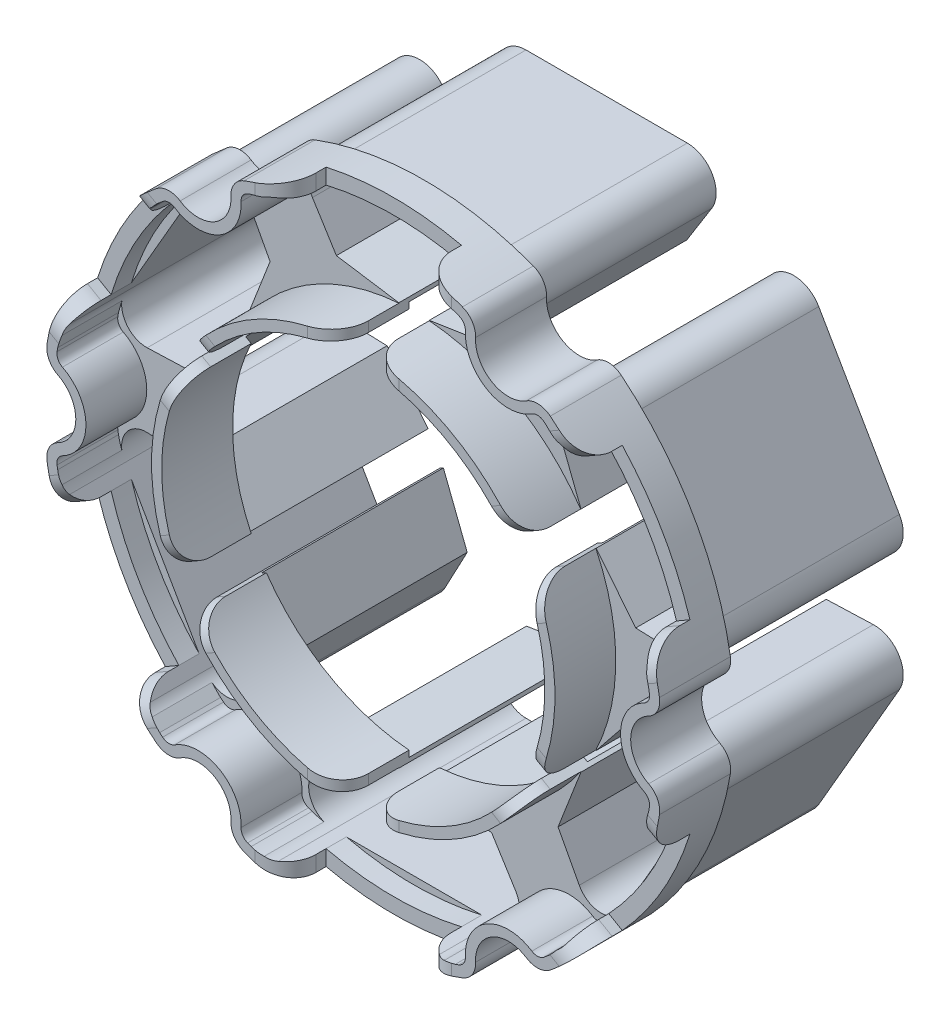
SolidWorks part; units mm, degrees
ref_plane "Ön Düzlem" through (0, 0, 0) normal (0, 0, 1) x (1, 0, 0)
ref_plane "Üst Düzlem" through (0, 0, 0) normal (0, 1, 0) x (1, 0, 0)
ref_plane "Sağ Düzlem" through (0, 0, 0) normal (1, 0, 0) x (0, 0, -1)
sketch "Çizim2" plane through (0, 0, 0) normal (0, 0, 1) x (1, 0, 0)
  line L0 (-1.5, 18.3137) -> (-1.5, 19.3137) construction
  line L13 (1.5, 18.3137) -> (1.5, 19.3137) construction
  line L14 (1.5, 19.3137) -> (8, 20.3137) construction
  line L15 (-1.5, 19.3137) -> (-8, 20.3137) construction
  line L16 (8, 20.3137) -> (10.5, 24.3137) construction
  line L17 (-8, 20.3137) -> (-10.5, 24.3137) construction
  line L18 (-7.956, 28.9037) -> (7.956, 28.9037) construction
  line L20 (-1.5, 19.4654) -> (-7.9092, 20.4515)
  line L21 (-7.9092, 20.4515) -> (-10.3728, 24.3932)
  line L22 (-7.956, 28.7537) -> (7.956, 28.7537)
  line L23 (7.9092, 20.4515) -> (10.3728, 24.3932)
  line L24 (1.5, 19.4654) -> (7.9092, 20.4515)
  line L27 (1.5, 19.8803) -> (7.6612, 20.8281)
  line L28 (7.6612, 20.8281) -> (10.0251, 24.6105)
  line L29 (-7.956, 28.3437) -> (7.956, 28.3437)
  line L30 (-7.6612, 20.8281) -> (-10.0251, 24.6105)
  line L31 (-1.5, 19.8803) -> (-7.6612, 20.8281)
  line L120 (-0.94, 18.3137) -> (-0.94, 19.7941) construction
  line L121 (-1.35, 18.3137) -> (-1.35, 19.4424) construction
  line L122 (1.35, 18.3137) -> (1.35, 19.4424) construction
  line L123 (0.94, 18.3137) -> (0.94, 19.7941) construction
  line L133 (-0.94, 19.7941) -> (-7.6612, 20.8281) construction
  line L134 (0.94, 19.7941) -> (7.6612, 20.8281) construction
  line L145 (-1.5, 19.8803) -> (-1.5, 19.4654)
  line L146 (1.5, 19.8803) -> (1.5, 19.4654)
  line L147 (17.8718, 8.7595) -> (21.8683, 3.7793) [skipped]
  line L148 (21.8683, 3.7793) -> (26.3259, 3.6232) [skipped]
  line L149 (20.5683, 21.0619) -> (28.5243, 7.2817) [skipped]
  line L150 (14.2071, 17.0488) -> (16.3007, 20.9872) [skipped]
  line L151 (16.5218, 11.0977) -> (14.2071, 17.0488) [skipped]
  line L152 (-1.35, 19.4424) -> (-7.9092, 20.4515) construction
  line L153 (16.1626, 10.8903) -> (13.7569, 17.0753) [skipped]
  line L154 (13.7569, 17.0753) -> (15.9387, 21.1797) [skipped]
  line L155 (20.9234, 21.2669) -> (28.8794, 7.4867) [skipped]
  line L156 (21.6661, 3.3761) -> (26.3115, 3.2135) [skipped]
  line L157 (17.5126, 8.552) -> (21.6661, 3.3761) [skipped]
  line L158 (1.35, 19.4424) -> (7.9092, 20.4515) construction
  line L159 (-17.8718, 8.7595) -> (-21.8683, 3.7793) [skipped]
  line L160 (-21.8683, 3.7793) -> (-26.3259, 3.6232) [skipped]
  line L161 (-28.5243, 7.2817) -> (-20.5683, 21.0619) [skipped]
  line L162 (-14.2071, 17.0488) -> (-16.3007, 20.9872) [skipped]
  line L163 (-16.5218, 11.0977) -> (-14.2071, 17.0488) [skipped]
  line L164 (16.4668, 11.2392) -> (14.2071, 17.0488)
  line L165 (-16.1626, 10.8903) -> (-13.7569, 17.0753) [skipped]
  line L166 (-13.7569, 17.0753) -> (-15.9387, 21.1797) [skipped]
  line L167 (-28.8794, 7.4867) -> (-20.9234, 21.2669) [skipped]
  line L168 (-21.6661, 3.3761) -> (-26.3115, 3.2135) [skipped]
  line L169 (-17.5126, 8.552) -> (-21.6661, 3.3761) [skipped]
  line L170 (14.2071, 17.0488) -> (16.3007, 20.9872)
  line L171 (17.5126, -8.552) -> (21.6661, -3.3761) [skipped]
  line L172 (21.6661, -3.3761) -> (26.3115, -3.2135) [skipped]
  line L173 (28.8794, -7.4867) -> (20.9234, -21.2669) [skipped]
  line L174 (13.7569, -17.0753) -> (15.9387, -21.1797) [skipped]
  line L175 (16.1626, -10.8903) -> (13.7569, -17.0753) [skipped]
  line L176 (20.5683, 21.0619) -> (28.5243, 7.2817)
  line L177 (16.5218, -11.0977) -> (14.2071, -17.0488) [skipped]
  line L178 (14.2071, -17.0488) -> (16.3007, -20.9872) [skipped]
  line L179 (28.5243, -7.2817) -> (20.5683, -21.0619) [skipped]
  line L180 (21.8683, -3.7793) -> (26.3259, -3.6232) [skipped]
  line L181 (17.8718, -8.7595) -> (21.8683, -3.7793) [skipped]
  line L182 (21.8683, 3.7793) -> (26.3259, 3.6232)
  line L183 (1.35, -19.4424) -> (7.9092, -20.4515) [skipped]
  line L184 (7.9092, -20.4515) -> (10.3728, -24.3932) [skipped]
  line L185 (7.956, -28.7537) -> (-7.956, -28.7537) [skipped]
  line L186 (-7.9092, -20.4515) -> (-10.3728, -24.3932) [skipped]
  line L187 (-1.35, -19.4424) -> (-7.9092, -20.4515) [skipped]
  line L188 (17.9668, 8.6411) -> (21.8683, 3.7793)
  line L189 (-1.35, -19.8572) -> (-7.6612, -20.8281) [skipped]
  line L190 (-7.6612, -20.8281) -> (-10.0251, -24.6105) [skipped]
  line L191 (7.956, -28.3437) -> (-7.956, -28.3437) [skipped]
  line L192 (7.6612, -20.8281) -> (10.0251, -24.6105) [skipped]
  line L193 (1.35, -19.8572) -> (7.6612, -20.8281) [skipped]
  line L194 (17.9668, 8.6411) -> (17.6076, 8.4337)
  line L195 (-16.1626, -10.8903) -> (-13.7569, -17.0753) [skipped]
  line L196 (-13.7569, -17.0753) -> (-15.9387, -21.1797) [skipped]
  line L197 (-20.9234, -21.2669) -> (-28.8794, -7.4867) [skipped]
  line L198 (-21.6661, -3.3761) -> (-26.3115, -3.2135) [skipped]
  line L199 (-17.5126, -8.552) -> (-21.6661, -3.3761) [skipped]
  line L200 (17.6076, 8.4337) -> (21.6661, 3.3761)
  line L201 (-17.8718, -8.7595) -> (-21.8683, -3.7793) [skipped]
  line L202 (-21.8683, -3.7793) -> (-26.3259, -3.6232) [skipped]
  line L203 (-20.5683, -21.0619) -> (-28.5243, -7.2817) [skipped]
  line L204 (-14.2071, -17.0488) -> (-16.3007, -20.9872) [skipped]
  line L205 (-16.5218, -11.0977) -> (-14.2071, -17.0488) [skipped]
  line L206 (21.6661, 3.3761) -> (26.3115, 3.2135)
  line L207 (20.9234, 21.2669) -> (28.8794, 7.4867)
  line L208 (13.7569, 17.0753) -> (15.9387, 21.1797)
  line L209 (16.1076, 11.0318) -> (13.7569, 17.0753)
  line L210 (16.4668, 11.2392) -> (16.1076, 11.0318)
  line L211 (17.9668, -8.6411) -> (21.8683, -3.7793)
  line L212 (21.8683, -3.7793) -> (26.3259, -3.6232)
  line L213 (28.5243, -7.2817) -> (20.5683, -21.0619)
  line L214 (14.2071, -17.0488) -> (16.3007, -20.9872)
  line L215 (16.4668, -11.2392) -> (14.2071, -17.0488)
  line L216 (16.4668, -11.2392) -> (16.1076, -11.0318)
  line L217 (16.1076, -11.0318) -> (13.7569, -17.0753)
  line L218 (13.7569, -17.0753) -> (15.9387, -21.1797)
  line L219 (28.8794, -7.4867) -> (20.9234, -21.2669)
  line L220 (21.6661, -3.3761) -> (26.3115, -3.2135)
  line L221 (17.6076, -8.4337) -> (21.6661, -3.3761)
  line L222 (17.9668, -8.6411) -> (17.6076, -8.4337)
  line L223 (1.5, -19.8803) -> (7.6612, -20.8281)
  line L224 (7.6612, -20.8281) -> (10.0251, -24.6105)
  line L225 (7.956, -28.3437) -> (-7.956, -28.3437)
  line L226 (-7.6612, -20.8281) -> (-10.0251, -24.6105)
  line L227 (-1.5, -19.8803) -> (-7.6612, -20.8281)
  line L228 (-1.5, -19.8803) -> (-1.5, -19.4654)
  line L229 (-1.5, -19.4654) -> (-7.9092, -20.4515)
  line L230 (-7.9092, -20.4515) -> (-10.3728, -24.3932)
  line L231 (7.956, -28.7537) -> (-7.956, -28.7537)
  line L232 (7.9092, -20.4515) -> (10.3728, -24.3932)
  line L233 (1.5, -19.4654) -> (7.9092, -20.4515)
  line L234 (1.5, -19.8803) -> (1.5, -19.4654)
  line L235 (-16.4668, -11.2392) -> (-14.2071, -17.0488)
  line L236 (-14.2071, -17.0488) -> (-16.3007, -20.9872)
  line L237 (-20.5683, -21.0619) -> (-28.5243, -7.2817)
  line L238 (-21.8683, -3.7793) -> (-26.3259, -3.6232)
  line L239 (-17.9668, -8.6411) -> (-21.8683, -3.7793)
  line L240 (-17.9668, -8.6411) -> (-17.6076, -8.4337)
  line L241 (-17.6076, -8.4337) -> (-21.6661, -3.3761)
  line L242 (-21.6661, -3.3761) -> (-26.3115, -3.2135)
  line L243 (-20.9234, -21.2669) -> (-28.8794, -7.4867)
  line L244 (-13.7569, -17.0753) -> (-15.9387, -21.1797)
  line L245 (-16.1076, -11.0318) -> (-13.7569, -17.0753)
  line L246 (-16.4668, -11.2392) -> (-16.1076, -11.0318)
  line L247 (-17.9668, 8.6411) -> (-21.8683, 3.7793)
  line L248 (-21.8683, 3.7793) -> (-26.3259, 3.6232)
  line L249 (-28.5243, 7.2817) -> (-20.5683, 21.0619)
  line L250 (-14.2071, 17.0488) -> (-16.3007, 20.9872)
  line L251 (-16.4668, 11.2392) -> (-14.2071, 17.0488)
  line L252 (-16.4668, 11.2392) -> (-16.1076, 11.0318)
  line L253 (-16.1076, 11.0318) -> (-13.7569, 17.0753)
  line L254 (-13.7569, 17.0753) -> (-15.9387, 21.1797)
  line L255 (-28.8794, 7.4867) -> (-20.9234, 21.2669)
  line L256 (-21.6661, 3.3761) -> (-26.3115, 3.2135)
  line L257 (-17.6076, 8.4337) -> (-21.6661, 3.3761)
  line L258 (-17.9668, 8.6411) -> (-17.6076, 8.4337)
  circle A0 centre (0, 0) radius 30.62 construction
  arc A1 (-7.956, 28.9037) -> (-10.5, 24.3137) centre (-7.956, 25.9037) ccw construction
  arc A2 (10.5, 24.3137) -> (7.956, 28.9037) centre (7.956, 25.9037) ccw construction
  circle A3 centre (-15.3101, 26.5179) radius 4.3797 construction
  circle A4 centre (-15.3101, 26.5179) radius 1.5 construction
  arc A5 (-7.956, 28.7537) -> (-10.3728, 24.3932) centre (-7.956, 25.9037) ccw
  arc A6 (10.3728, 24.3932) -> (7.956, 28.7537) centre (7.956, 25.9037) ccw
  arc A7 (10.0251, 24.6105) -> (7.956, 28.3437) centre (7.956, 25.9037) ccw
  arc A8 (-7.956, 28.3437) -> (-10.0251, 24.6105) centre (-7.956, 25.9037) ccw
  circle A9 centre (15.3101, 26.5179) radius 1.5 construction
  circle A14 centre (30.6203, 0) radius 1.5 construction
  circle A19 centre (15.3101, -26.5179) radius 1.5 construction
  circle A24 centre (-15.3101, -26.5179) radius 1.5 construction
  circle A29 centre (-30.6203, 0) radius 1.5 construction
  arc A34 (26.3259, 3.6232) -> (28.5243, 7.2817) centre (26.4112, 6.0617) ccw [skipped]
  arc A35 (20.5683, 21.0619) -> (16.3007, 20.9872) centre (18.4552, 19.8419) ccw [skipped]
  arc A36 (20.9234, 21.2669) -> (15.9387, 21.1797) centre (18.4552, 19.8419) ccw [skipped]
  arc A37 (26.3115, 3.2135) -> (28.8794, 7.4867) centre (26.4112, 6.0617) ccw [skipped]
  arc A38 (-28.5243, 7.2817) -> (-26.3259, 3.6232) centre (-26.4112, 6.0617) ccw [skipped]
  arc A39 (-16.3007, 20.9872) -> (-20.5683, 21.0619) centre (-18.4552, 19.8419) ccw [skipped]
  arc A40 (-15.9387, 21.1797) -> (-20.9234, 21.2669) centre (-18.4552, 19.8419) ccw [skipped]
  arc A41 (-28.8794, 7.4867) -> (-26.3115, 3.2135) centre (-26.4112, 6.0617) ccw [skipped]
  arc A42 (28.8794, -7.4867) -> (26.3115, -3.2135) centre (26.4112, -6.0617) ccw [skipped]
  arc A43 (15.9387, -21.1797) -> (20.9234, -21.2669) centre (18.4552, -19.8419) ccw [skipped]
  arc A44 (16.3007, -20.9872) -> (20.5683, -21.0619) centre (18.4552, -19.8419) ccw [skipped]
  arc A45 (28.5243, -7.2817) -> (26.3259, -3.6232) centre (26.4112, -6.0617) ccw [skipped]
  arc A46 (7.956, -28.7537) -> (10.3728, -24.3932) centre (7.956, -25.9037) ccw [skipped]
  arc A47 (-10.3728, -24.3932) -> (-7.956, -28.7537) centre (-7.956, -25.9037) ccw [skipped]
  arc A48 (-10.0251, -24.6105) -> (-7.956, -28.3437) centre (-7.956, -25.9037) ccw [skipped]
  arc A49 (7.956, -28.3437) -> (10.0251, -24.6105) centre (7.956, -25.9037) ccw [skipped]
  arc A50 (-20.9234, -21.2669) -> (-15.9387, -21.1797) centre (-18.4552, -19.8419) ccw [skipped]
  arc A51 (-26.3115, -3.2135) -> (-28.8794, -7.4867) centre (-26.4112, -6.0617) ccw [skipped]
  arc A52 (-26.3259, -3.6232) -> (-28.5243, -7.2817) centre (-26.4112, -6.0617) ccw [skipped]
  arc A53 (-20.5683, -21.0619) -> (-16.3007, -20.9872) centre (-18.4552, -19.8419) ccw [skipped]
  arc A54 (20.5683, 21.0619) -> (16.3007, 20.9872) centre (18.4552, 19.8419) ccw
  arc A55 (26.3259, 3.6232) -> (28.5243, 7.2817) centre (26.4112, 6.0617) ccw
  arc A56 (26.3115, 3.2135) -> (28.8794, 7.4867) centre (26.4112, 6.0617) ccw
  arc A57 (20.9234, 21.2669) -> (15.9387, 21.1797) centre (18.4552, 19.8419) ccw
  arc A58 (28.5243, -7.2817) -> (26.3259, -3.6232) centre (26.4112, -6.0617) ccw
  arc A59 (16.3007, -20.9872) -> (20.5683, -21.0619) centre (18.4552, -19.8419) ccw
  arc A60 (15.9387, -21.1797) -> (20.9234, -21.2669) centre (18.4552, -19.8419) ccw
  arc A61 (28.8794, -7.4867) -> (26.3115, -3.2135) centre (26.4112, -6.0617) ccw
  arc A62 (7.956, -28.3437) -> (10.0251, -24.6105) centre (7.956, -25.9037) ccw
  arc A63 (-10.0251, -24.6105) -> (-7.956, -28.3437) centre (-7.956, -25.9037) ccw
  arc A64 (-10.3728, -24.3932) -> (-7.956, -28.7537) centre (-7.956, -25.9037) ccw
  arc A65 (7.956, -28.7537) -> (10.3728, -24.3932) centre (7.956, -25.9037) ccw
  arc A66 (-20.5683, -21.0619) -> (-16.3007, -20.9872) centre (-18.4552, -19.8419) ccw
  arc A67 (-26.3259, -3.6232) -> (-28.5243, -7.2817) centre (-26.4112, -6.0617) ccw
  arc A68 (-26.3115, -3.2135) -> (-28.8794, -7.4867) centre (-26.4112, -6.0617) ccw
  arc A69 (-20.9234, -21.2669) -> (-15.9387, -21.1797) centre (-18.4552, -19.8419) ccw
  arc A70 (-28.5243, 7.2817) -> (-26.3259, 3.6232) centre (-26.4112, 6.0617) ccw
  arc A71 (-16.3007, 20.9872) -> (-20.5683, 21.0619) centre (-18.4552, 19.8419) ccw
  arc A72 (-15.9387, 21.1797) -> (-20.9234, 21.2669) centre (-18.4552, 19.8419) ccw
  arc A73 (-28.8794, 7.4867) -> (-26.3115, 3.2135) centre (-26.4112, 6.0617) ccw
  point P159 (0, 0)
  point P176 (0, 0)
  point P189 (0, 0)
  dimension "D1" = 61.24
  dimension "D8" = 3
  dimension "D9" = 3
  dimension "D10" = 3
  dimension "D11" = 7.3541
  dimension "D12" = 4.8101
  dimension "D14" = 15.912
  dimension "D2" = 4
  dimension "D3" = 4
  dimension "D4" = 6.5
  dimension "D5" = 6.5
  dimension "D6" = 1
  dimension "D7" = 1
  dimension "D13" = 2.2043
  dimension "D15" = 3
  dimension "D16" = 1
  dimension "D17" = 1
  dimension "D18" = 21
  dimension "D19" = 1.5
  dimension "D20" = 18.375
  dimension "D24" = 6
  dimension "D25" = 3
  dimension "D26" = 1.5
  dimension "D21" = 0.15
  dimension "D22" = 0.41
  dimension "D23" = 6
extrude "Yükseklik-Ekstrüzyon1" add sketch "Çizim2" along normal blind 18
sketch "Çizim3" plane through (0, 0, 18) normal (0, 0, 1) x (1, 0, 0)
  line L71 (10.0251, 24.6105) -> (7.6612, 20.8281) construction
  line L72 (7.6612, 20.8281) -> (1.5, 19.8803) construction
  line L73 (-7.956, 28.3437) -> (7.956, 28.3437) construction
  line L74 (-1.5, 19.8803) -> (-7.6612, 20.8281) construction
  line L75 (-7.6612, 20.8281) -> (-10.0251, 24.6105) construction
  line L76 (10.0251, 24.6105) -> (7.6612, 20.8281)
  line L77 (7.6612, 20.8281) -> (1.5, 19.8803)
  line L78 (-7.956, 28.3437) -> (7.956, 28.3437)
  line L79 (-1.5, 19.8803) -> (-7.6612, 20.8281)
  line L80 (-7.6612, 20.8281) -> (-10.0251, 24.6105)
  line L81 (-1.5, 19.8803) -> (-1.5, 18.8404)
  line L82 (1.5, 19.8803) -> (1.5, 18.8404)
  line L83 (17.9668, 8.6411) -> (17.0662, 8.1212)
  line L84 (21.8683, 3.7793) -> (17.9668, 8.6411)
  line L85 (26.3259, 3.6232) -> (21.8683, 3.7793)
  line L86 (20.5683, 21.0619) -> (28.5243, 7.2817)
  line L87 (14.2071, 17.0488) -> (16.3007, 20.9872)
  line L88 (16.4668, 11.2392) -> (14.2071, 17.0488)
  line L89 (16.4668, 11.2392) -> (15.5662, 10.7192)
  line L90 (16.4668, -11.2392) -> (15.5662, -10.7192)
  line L91 (14.2071, -17.0488) -> (16.4668, -11.2392)
  line L92 (16.3007, -20.9872) -> (14.2071, -17.0488)
  line L93 (28.5243, -7.2817) -> (20.5683, -21.0619)
  line L94 (21.8683, -3.7793) -> (26.3259, -3.6232)
  line L95 (17.9668, -8.6411) -> (21.8683, -3.7793)
  line L96 (17.9668, -8.6411) -> (17.0662, -8.1212)
  line L97 (-1.5, -19.8803) -> (-1.5, -18.8404)
  line L98 (-7.6612, -20.8281) -> (-1.5, -19.8803)
  line L99 (-10.0251, -24.6105) -> (-7.6612, -20.8281)
  line L100 (7.956, -28.3437) -> (-7.956, -28.3437)
  line L101 (7.6612, -20.8281) -> (10.0251, -24.6105)
  line L102 (1.5, -19.8803) -> (7.6612, -20.8281)
  line L103 (1.5, -19.8803) -> (1.5, -18.8404)
  line L104 (-17.9668, -8.6411) -> (-17.0662, -8.1212)
  line L105 (-21.8683, -3.7793) -> (-17.9668, -8.6411)
  line L106 (-26.3259, -3.6232) -> (-21.8683, -3.7793)
  line L107 (-20.5683, -21.0619) -> (-28.5243, -7.2817)
  line L108 (-14.2071, -17.0488) -> (-16.3007, -20.9872)
  line L109 (-16.4668, -11.2392) -> (-14.2071, -17.0488)
  line L110 (-16.4668, -11.2392) -> (-15.5662, -10.7192)
  line L111 (-16.4668, 11.2392) -> (-15.5662, 10.7192)
  line L112 (-14.2071, 17.0488) -> (-16.4668, 11.2392)
  line L113 (-16.3007, 20.9872) -> (-14.2071, 17.0488)
  line L114 (-28.5243, 7.2817) -> (-20.5683, 21.0619)
  line L115 (-21.8683, 3.7793) -> (-26.3259, 3.6232)
  line L116 (-17.9668, 8.6411) -> (-21.8683, 3.7793)
  line L117 (-17.9668, 8.6411) -> (-17.0662, 8.1212)
  arc A0 (-18.0344, 24.7456) -> (-30.4475, 3.2454) centre (0, 0) ccw
  circle A1 centre (-15.31, 26.5177) radius 4.5296 construction
  arc A3 (-7.956, 28.7537) -> (-10.3728, 24.3932) centre (-7.956, 25.9037) ccw construction
  arc A4 (-18.0344, 24.7456) -> (-12.4131, 27.991) centre (-15.31, 26.5177) ccw
  arc A5 (12.4131, 27.991) -> (18.0344, 24.7456) centre (15.31, 26.5177) ccw
  arc A6 (30.4475, 3.2454) -> (30.4475, -3.2454) centre (30.62, 0) ccw
  arc A7 (18.0344, -24.7456) -> (12.4131, -27.991) centre (15.31, -26.5177) ccw
  arc A8 (-12.4131, -27.991) -> (-18.0344, -24.7456) centre (-15.31, -26.5177) ccw
  arc A9 (-30.4475, -3.2454) -> (-30.4475, 3.2454) centre (-30.62, 0) ccw
  arc A10 (12.4131, 27.991) -> (-12.4131, 27.991) centre (0, 0) ccw
  arc A11 (30.4475, 3.2454) -> (18.0344, 24.7456) centre (0, 0) ccw
  arc A12 (18.0344, -24.7456) -> (30.4475, -3.2454) centre (0, 0) ccw
  arc A13 (-12.4131, -27.991) -> (12.4131, -27.991) centre (0, 0) ccw
  arc A14 (-30.4475, -3.2454) -> (-18.0344, -24.7456) centre (0, 0) ccw
  arc A35 (-1.5, 18.8404) -> (-15.5662, 10.7192) centre (0, 0) ccw
  arc A36 (10.0251, 24.6105) -> (7.956, 28.3437) centre (7.956, 25.9037) ccw construction
  arc A37 (-7.956, 28.3437) -> (-10.0251, 24.6105) centre (-7.956, 25.9037) ccw construction
  arc A38 (10.0251, 24.6105) -> (7.956, 28.3437) centre (7.956, 25.9037) ccw
  arc A39 (-7.956, 28.3437) -> (-10.0251, 24.6105) centre (-7.956, 25.9037) ccw
  arc A40 (26.3259, 3.6232) -> (28.5243, 7.2817) centre (26.4112, 6.0617) ccw
  arc A41 (20.5683, 21.0619) -> (16.3007, 20.9872) centre (18.4552, 19.8419) ccw
  arc A42 (16.3007, -20.9872) -> (20.5683, -21.0619) centre (18.4552, -19.8419) ccw
  arc A43 (28.5243, -7.2817) -> (26.3259, -3.6232) centre (26.4112, -6.0617) ccw
  arc A44 (-10.0251, -24.6105) -> (-7.956, -28.3437) centre (-7.956, -25.9037) ccw
  arc A45 (7.956, -28.3437) -> (10.0251, -24.6105) centre (7.956, -25.9037) ccw
  arc A46 (-26.3259, -3.6232) -> (-28.5243, -7.2817) centre (-26.4112, -6.0617) ccw
  arc A47 (-20.5683, -21.0619) -> (-16.3007, -20.9872) centre (-18.4552, -19.8419) ccw
  arc A48 (-16.3007, 20.9872) -> (-20.5683, 21.0619) centre (-18.4552, 19.8419) ccw
  arc A49 (-28.5243, 7.2817) -> (-26.3259, 3.6232) centre (-26.4112, 6.0617) ccw
  arc A50 (15.5662, 10.7192) -> (1.5, 18.8404) centre (0, 0) ccw
  arc A51 (17.0662, -8.1212) -> (17.0662, 8.1212) centre (0, 0) ccw
  arc A52 (1.5, -18.8404) -> (15.5662, -10.7192) centre (0, 0) ccw
  arc A53 (-15.5662, -10.7192) -> (-1.5, -18.8404) centre (0, 0) ccw
  arc A54 (-17.0662, 8.1212) -> (-17.0662, -8.1212) centre (0, 0) ccw
  arc A55 (-15.9387, 21.1797) -> (-20.9234, 21.2669) centre (-18.4552, 19.8419) ccw construction
  point P30 (0, 0)
  point P102 (0, 0)
  point P103 (0, 0)
  point P141 (0, 0)
  dimension "D1" = 61.24
  dimension "D2" = 6.5
  dimension "D4" = 37.8
  dimension "D3" = 6
  dimension "D5" = 6
extrude "Yükseklik-Ekstrüzyon2" add sketch "Çizim3" along normal blind 1
fillet "Radyus2" radius 2 12 edges at (18.0344, 24.7456, 18.5) (12.4131, 27.991, 18.5) (30.4475, 3.2454, 18.5) (30.4475, -3.2454, 18.5) (12.4131, -27.991, 18.5) (18.0344, -24.7456, 18.5) (-12.4131, -27.991, 18.5) (-18.0344, -24.7456, 18.5) (-30.4475, -3.2454, 18.5) (-30.4475, 3.2454, 18.5) (-12.4131, 27.991, 18.5) (-18.0344, 24.7456, 18.5)
sketch "Çizim4" plane through (0, 0, 19) normal (0, 0, 1) x (1, 0, 0)
  line L0 (-1.5, 18.8404) -> (-1.5, 19.8434)
  line L1 (-1.5, 19.8803) -> (-1.5, 18.8404) construction
  line L2 (1.5, 18.8404) -> (1.5, 19.8434)
  line L3 (1.5, 18.8404) -> (1.5, 19.8803) construction
  line L4 (15.5662, 10.7192) -> (16.4349, 11.2207)
  line L5 (17.0662, 8.1212) -> (17.9349, 8.6227)
  line L6 (17.0662, -8.1212) -> (17.9349, -8.6227)
  line L7 (15.5662, -10.7192) -> (16.4349, -11.2207)
  line L8 (1.5, -18.8404) -> (1.5, -19.8434)
  line L9 (-1.5, -18.8404) -> (-1.5, -19.8434)
  line L10 (-15.5662, -10.7192) -> (-16.4349, -11.2207)
  line L11 (-17.0662, -8.1212) -> (-17.9349, -8.6227)
  line L12 (-17.0662, 8.1212) -> (-17.9349, 8.6227)
  line L13 (-15.5662, 10.7192) -> (-16.4349, 11.2207)
  arc A0 (-15.5662, -10.7192) -> (-1.5, -18.8404) centre (0, 0) ccw construction
  arc A1 (1.5, -18.8404) -> (15.5662, -10.7192) centre (0, 0) ccw construction
  arc A2 (17.0662, -8.1212) -> (17.0662, 8.1212) centre (0, 0) ccw construction
  arc A3 (15.5662, 10.7192) -> (1.5, 18.8404) centre (0, 0) ccw construction
  arc A4 (-1.5, 18.8404) -> (-15.5662, 10.7192) centre (0, 0) ccw construction
  arc A5 (-17.0662, 8.1212) -> (-17.0662, -8.1212) centre (0, 0) ccw construction
  arc A6 (-15.5662, -10.7192) -> (-1.5, -18.8404) centre (0, 0) ccw
  arc A7 (1.5, -18.8404) -> (15.5662, -10.7192) centre (0, 0) ccw
  arc A8 (17.0662, -8.1212) -> (17.0662, 8.1212) centre (0, 0) ccw
  arc A9 (15.5662, 10.7192) -> (1.5, 18.8404) centre (0, 0) ccw
  arc A10 (-1.5, 18.8404) -> (-15.5662, 10.7192) centre (0, 0) ccw
  arc A11 (-17.0662, 8.1212) -> (-17.0662, -8.1212) centre (0, 0) ccw
  arc A12 (-17.9349, 8.6227) -> (-17.9349, -8.6227) centre (0, 0) ccw
  arc A13 (-1.5, 19.8434) -> (-16.4349, 11.2207) centre (0, 0) ccw
  arc A14 (16.4349, 11.2207) -> (1.5, 19.8434) centre (0, 0) ccw
  arc A15 (17.9349, -8.6227) -> (17.9349, 8.6227) centre (0, 0) ccw
  arc A16 (1.5, -19.8434) -> (16.4349, -11.2207) centre (0, 0) ccw
  arc A17 (-16.4349, -11.2207) -> (-1.5, -19.8434) centre (0, 0) ccw
  point P47 (0, 0)
  dimension "D1" = 1
  dimension "D2" = 6
extrude "Yükseklik-Ekstrüzyon3" add sketch "Çizim4" along normal blind 6
fillet "Radyus3" radius 3 12 edges at (-16.0006, -10.97, 25) (-1.5, -19.3419, 25) (1.5, -19.3419, 25) (16.0006, -10.97, 25) (17.5006, 8.3719, 25) (17.5006, -8.3719, 25) (16.0006, 10.97, 25) (1.5, 19.3419, 25) (-1.5, 19.3419, 25) (-16.0006, 10.97, 25) (-17.5006, 8.3719, 25) (-17.5006, -8.3719, 25)
sketch "Çizim5" plane through (0, 0, 19) normal (0, 0, 1) x (1, 0, 0)
  line L0 (-28.5243, -7.2817) -> (-20.5683, -21.0619) construction
  line L1 (-7.956, -28.3437) -> (7.956, -28.3437) construction
  line L2 (20.5683, -21.0619) -> (28.5243, -7.2817) construction
  line L3 (28.5243, 7.2817) -> (20.5683, 21.0619) construction
  line L4 (-20.5683, 21.0619) -> (-28.5243, 7.2817) construction
  line L5 (-28.5243, -7.2817) -> (-27.8859, -8.3875)
  line L6 (-7.956, -28.3437) -> (-6.6791, -28.3437)
  line L7 (20.5683, -21.0619) -> (21.2068, -19.9561)
  line L8 (28.5243, 7.2817) -> (27.8859, 8.3875)
  line L9 (-20.5683, 21.0619) -> (-21.2068, 19.9561)
  line L10 (-27.8859, 8.3875) -> (-28.5243, 7.2817)
  line L11 (-21.2068, -19.9561) -> (-20.5683, -21.0619)
  line L12 (6.6791, -28.3437) -> (7.956, -28.3437)
  line L13 (27.8859, -8.3875) -> (28.5243, -7.2817)
  line L14 (21.2068, 19.9561) -> (20.5683, 21.0619)
  line L15 (7.956, 28.3437) -> (-7.956, 28.3437) construction
  line L16 (7.956, 28.3437) -> (6.6791, 28.3437)
  line L17 (-6.6791, 28.3437) -> (-7.956, 28.3437)
  arc A0 (28.7285, 4.7588) -> (28.6651, 5.127) centre (0, 0) ccw
  arc A1 (18.4855, 22.5002) -> (17.8959, 22.5333) centre (18.1681, 22.1139) ccw
  arc A2 (10.5664, 26.765) -> (17.8959, 22.5333) centre (15.31, 26.5177) ccw
  arc A3 (10.5664, 26.765) -> (10.243, 27.259) centre (10.0671, 26.791) ccw
  arc A4 (10.243, 27.259) -> (9.8924, 27.3882) centre (0, 0) ccw
  arc A5 (-10.243, 27.259) -> (-10.5664, 26.765) centre (-10.0671, 26.791) ccw
  arc A6 (-17.8959, 22.5333) -> (-10.5664, 26.765) centre (-15.31, 26.5177) ccw
  arc A7 (-17.8959, 22.5333) -> (-18.4855, 22.5002) centre (-18.1681, 22.1139) ccw
  arc A8 (-18.4855, 22.5002) -> (-18.7727, 22.2612) centre (0, 0) ccw
  arc A9 (-28.7285, 4.7588) -> (-28.4624, 4.2317) centre (-28.2352, 4.6771) ccw
  arc A10 (-28.4624, -4.2317) -> (-28.4624, 4.2317) centre (-30.62, 0) ccw
  arc A11 (-28.4624, -4.2317) -> (-28.7285, -4.7588) centre (-28.2352, -4.6771) ccw
  arc A12 (-28.7285, -4.7588) -> (-28.6651, -5.127) centre (0, 0) ccw
  arc A13 (-18.4855, -22.5002) -> (-17.8959, -22.5333) centre (-18.1681, -22.1139) ccw
  arc A14 (-10.5664, -26.765) -> (-17.8959, -22.5333) centre (-15.31, -26.5177) ccw
  arc A15 (-10.5664, -26.765) -> (-10.243, -27.259) centre (-10.0671, -26.791) ccw
  arc A16 (-10.243, -27.259) -> (-9.8924, -27.3882) centre (0, 0) ccw
  arc A17 (10.243, -27.259) -> (10.5664, -26.765) centre (10.0671, -26.791) ccw
  arc A18 (17.8959, -22.5333) -> (10.5664, -26.765) centre (15.31, -26.5177) ccw
  arc A19 (17.8959, -22.5333) -> (18.4855, -22.5002) centre (18.1681, -22.1139) ccw
  arc A20 (18.4855, -22.5002) -> (18.7727, -22.2612) centre (0, 0) ccw
  arc A21 (28.7285, -4.7588) -> (28.4624, -4.2317) centre (28.2352, -4.6771) ccw
  arc A22 (28.4624, 4.2317) -> (28.4624, -4.2317) centre (30.62, 0) ccw
  arc A23 (28.4624, 4.2317) -> (28.7285, 4.7588) centre (28.2352, 4.6771) ccw
  arc A24 (30.2084, 5.004) -> (19.4377, 23.6592) centre (0, 0) ccw
  arc A25 (19.4377, 23.6592) -> (17.0793, 23.7915) centre (18.1681, 22.1139) ccw
  arc A26 (12.0644, 26.6869) -> (17.0793, 23.7915) centre (15.31, 26.5177) ccw
  arc A27 (12.0644, 26.6869) -> (10.7706, 28.6632) centre (10.0671, 26.791) ccw
  arc A28 (10.7706, 28.6632) -> (-10.7706, 28.6632) centre (0, 0) ccw
  arc A29 (-10.7706, 28.6632) -> (-12.0644, 26.6869) centre (-10.0671, 26.791) ccw
  arc A30 (-17.0793, 23.7915) -> (-12.0644, 26.6869) centre (-15.31, 26.5177) ccw
  arc A31 (-17.0793, 23.7915) -> (-19.4377, 23.6592) centre (-18.1681, 22.1139) ccw
  arc A32 (-19.4377, 23.6592) -> (-30.2084, 5.004) centre (0, 0) ccw
  arc A33 (-30.2084, 5.004) -> (-29.1437, 2.8954) centre (-28.2352, 4.6771) ccw
  arc A34 (-29.1437, -2.8954) -> (-29.1437, 2.8954) centre (-30.62, 0) ccw
  arc A35 (-29.1437, -2.8954) -> (-30.2084, -5.004) centre (-28.2352, -4.6771) ccw
  arc A36 (-30.2084, -5.004) -> (-19.4377, -23.6592) centre (0, 0) ccw
  arc A37 (-19.4377, -23.6592) -> (-17.0793, -23.7915) centre (-18.1681, -22.1139) ccw
  arc A38 (-12.0644, -26.6869) -> (-17.0793, -23.7915) centre (-15.31, -26.5177) ccw
  arc A39 (-12.0644, -26.6869) -> (-10.7706, -28.6632) centre (-10.0671, -26.791) ccw
  arc A40 (-10.7706, -28.6632) -> (10.7706, -28.6632) centre (0, 0) ccw
  arc A41 (10.7706, -28.6632) -> (12.0644, -26.6869) centre (10.0671, -26.791) ccw
  arc A42 (17.0793, -23.7915) -> (12.0644, -26.6869) centre (15.31, -26.5177) ccw
  arc A43 (17.0793, -23.7915) -> (19.4377, -23.6592) centre (18.1681, -22.1139) ccw
  arc A44 (19.4377, -23.6592) -> (30.2084, -5.004) centre (0, 0) ccw
  arc A45 (30.2084, -5.004) -> (29.1437, -2.8954) centre (28.2352, -4.6771) ccw
  arc A46 (29.1437, 2.8954) -> (29.1437, -2.8954) centre (30.62, 0) ccw
  arc A47 (29.1437, 2.8954) -> (30.2084, 5.004) centre (28.2352, 4.6771) ccw
  arc A48 (30.2084, 5.004) -> (19.4377, 23.6592) centre (0, 0) ccw
  arc A49 (19.4377, 23.6592) -> (17.0793, 23.7915) centre (18.1681, 22.1139) ccw
  arc A50 (12.0644, 26.6869) -> (17.0793, 23.7915) centre (15.31, 26.5177) ccw
  arc A51 (12.0644, 26.6869) -> (10.7706, 28.6632) centre (10.0671, 26.791) ccw
  arc A52 (10.7706, 28.6632) -> (-10.7706, 28.6632) centre (0, 0) ccw
  arc A53 (-10.7706, 28.6632) -> (-12.0644, 26.6869) centre (-10.0671, 26.791) ccw
  arc A54 (-17.0793, 23.7915) -> (-12.0644, 26.6869) centre (-15.31, 26.5177) ccw
  arc A55 (-17.0793, 23.7915) -> (-19.4377, 23.6592) centre (-18.1681, 22.1139) ccw
  arc A56 (-19.4377, 23.6592) -> (-30.2084, 5.004) centre (0, 0) ccw
  arc A57 (-30.2084, 5.004) -> (-29.1437, 2.8954) centre (-28.2352, 4.6771) ccw
  arc A58 (-29.1437, -2.8954) -> (-29.1437, 2.8954) centre (-30.62, 0) ccw
  arc A59 (-29.1437, -2.8954) -> (-30.2084, -5.004) centre (-28.2352, -4.6771) ccw
  arc A60 (-30.2084, -5.004) -> (-19.4377, -23.6592) centre (0, 0) ccw
  arc A61 (-19.4377, -23.6592) -> (-17.0793, -23.7915) centre (-18.1681, -22.1139) ccw
  arc A62 (-12.0644, -26.6869) -> (-17.0793, -23.7915) centre (-15.31, -26.5177) ccw
  arc A63 (-12.0644, -26.6869) -> (-10.7706, -28.6632) centre (-10.0671, -26.791) ccw
  arc A64 (-10.7706, -28.6632) -> (10.7706, -28.6632) centre (0, 0) ccw
  arc A65 (10.7706, -28.6632) -> (12.0644, -26.6869) centre (10.0671, -26.791) ccw
  arc A66 (17.0793, -23.7915) -> (12.0644, -26.6869) centre (15.31, -26.5177) ccw
  arc A67 (17.0793, -23.7915) -> (19.4377, -23.6592) centre (18.1681, -22.1139) ccw
  arc A68 (19.4377, -23.6592) -> (30.2084, -5.004) centre (0, 0) ccw
  arc A69 (30.2084, -5.004) -> (29.1437, -2.8954) centre (28.2352, -4.6771) ccw
  arc A70 (29.1437, 2.8954) -> (29.1437, -2.8954) centre (30.62, 0) ccw
  arc A71 (29.1437, 2.8954) -> (30.2084, 5.004) centre (28.2352, 4.6771) ccw
  arc A72 (-28.5243, 7.2817) -> (-26.3259, 3.6232) centre (-26.4112, 6.0617) ccw construction
  arc A73 (-26.3259, -3.6232) -> (-28.5243, -7.2817) centre (-26.4112, -6.0617) ccw construction
  arc A74 (-20.5683, -21.0619) -> (-16.3007, -20.9872) centre (-18.4552, -19.8419) ccw construction
  arc A75 (-10.0251, -24.6105) -> (-7.956, -28.3437) centre (-7.956, -25.9037) ccw construction
  arc A76 (7.956, -28.3437) -> (10.0251, -24.6105) centre (7.956, -25.9037) ccw construction
  arc A77 (16.3007, -20.9872) -> (20.5683, -21.0619) centre (18.4552, -19.8419) ccw construction
  arc A78 (28.5243, -7.2817) -> (26.3259, -3.6232) centre (26.4112, -6.0617) ccw construction
  arc A79 (26.3259, 3.6232) -> (28.5243, 7.2817) centre (26.4112, 6.0617) ccw construction
  arc A80 (20.5683, 21.0619) -> (16.3007, 20.9872) centre (18.4552, 19.8419) ccw construction
  arc A81 (10.0251, 24.6105) -> (7.956, 28.3437) centre (7.956, 25.9037) ccw construction
  arc A82 (-7.956, 28.3437) -> (-10.0251, 24.6105) centre (-7.956, 25.9037) ccw construction
  arc A83 (-16.3007, 20.9872) -> (-20.5683, 21.0619) centre (-18.4552, 19.8419) ccw construction
  arc A84 (-28.5243, 7.2817) -> (-28.6651, 5.127) centre (-26.4112, 6.0617) ccw
  arc A85 (-28.6651, -5.127) -> (-28.5243, -7.2817) centre (-26.4112, -6.0617) ccw
  arc A86 (-20.5683, -21.0619) -> (-18.7727, -22.2612) centre (-18.4552, -19.8419) ccw
  arc A87 (-9.8924, -27.3882) -> (-7.956, -28.3437) centre (-7.956, -25.9037) ccw
  arc A88 (7.956, -28.3437) -> (9.8924, -27.3882) centre (7.956, -25.9037) ccw
  arc A89 (18.7727, -22.2612) -> (20.5683, -21.0619) centre (18.4552, -19.8419) ccw
  arc A90 (28.5243, -7.2817) -> (28.6651, -5.127) centre (26.4112, -6.0617) ccw
  arc A91 (28.6651, 5.127) -> (28.5243, 7.2817) centre (26.4112, 6.0617) ccw
  arc A92 (20.5683, 21.0619) -> (18.7727, 22.2612) centre (18.4552, 19.8419) ccw
  arc A93 (9.8924, 27.3882) -> (7.956, 28.3437) centre (7.956, 25.9037) ccw
  arc A94 (-7.956, 28.3437) -> (-9.8924, 27.3882) centre (-7.956, 25.9037) ccw
  arc A95 (-18.7727, 22.2612) -> (-20.5683, 21.0619) centre (-18.4552, 19.8419) ccw
  arc A96 (-21.2068, 19.9561) -> (-27.8859, 8.3875) centre (0, 0) ccw
  arc A97 (-18.4855, 22.5002) -> (-28.7285, 4.7588) centre (0, 0) ccw construction
  arc A98 (-28.6651, 5.127) -> (-28.7285, 4.7588) centre (0, 0) ccw
  arc A99 (-27.8859, -8.3875) -> (-21.2068, -19.9561) centre (0, 0) ccw
  arc A100 (-28.7285, -4.7588) -> (-18.4855, -22.5002) centre (0, 0) ccw construction
  arc A101 (-18.7727, -22.2612) -> (-18.4855, -22.5002) centre (0, 0) ccw
  arc A102 (-6.6791, -28.3437) -> (6.6791, -28.3437) centre (0, 0) ccw
  arc A103 (-10.243, -27.259) -> (10.243, -27.259) centre (0, 0) ccw construction
  arc A104 (9.8924, -27.3882) -> (10.243, -27.259) centre (0, 0) ccw
  arc A105 (21.2068, -19.9561) -> (27.8859, -8.3875) centre (0, 0) ccw
  arc A106 (18.4855, -22.5002) -> (28.7285, -4.7588) centre (0, 0) ccw construction
  arc A107 (28.6651, -5.127) -> (28.7285, -4.7588) centre (0, 0) ccw
  arc A108 (27.8859, 8.3875) -> (21.2068, 19.9561) centre (0, 0) ccw
  arc A109 (28.7285, 4.7588) -> (18.4855, 22.5002) centre (0, 0) ccw construction
  arc A110 (18.7727, 22.2612) -> (18.4855, 22.5002) centre (0, 0) ccw
  arc A111 (6.6791, 28.3437) -> (-6.6791, 28.3437) centre (0, 0) ccw
  arc A112 (10.243, 27.259) -> (-10.243, 27.259) centre (0, 0) ccw construction
  arc A113 (-9.8924, 27.3882) -> (-10.243, 27.259) centre (0, 0) ccw
  dimension "D1" = 0
  dimension "D2" = 1.5
extrude "Yükseklik-Ekstrüzyon4" add sketch "Çizim5" along normal blind 6
sketch "Çizim6" plane through (0, 0, 25) normal (0, 0, 1) x (1, 0, 0)
  line L0 (-6.6791, 28.3437) -> (-6.6791, 29.8827)
  line L1 (6.6791, 28.3437) -> (6.6791, 29.8827)
  line L2 (21.2068, 19.9561) -> (22.5396, 20.7256)
  line L3 (27.8859, 8.3875) -> (29.2187, 9.157)
  line L4 (27.8859, -8.3875) -> (29.2187, -9.157)
  line L5 (21.2068, -19.9561) -> (22.5396, -20.7256)
  line L6 (6.6791, -28.3437) -> (6.6791, -29.8827)
  line L7 (-6.6791, -28.3437) -> (-6.6791, -29.8827)
  line L8 (-21.2068, -19.9561) -> (-22.5396, -20.7256)
  line L9 (-27.8859, -8.3875) -> (-29.2187, -9.157)
  line L10 (-27.8859, 8.3875) -> (-29.2187, 9.157)
  line L11 (-21.2068, 19.9561) -> (-22.5396, 20.7256)
  line L12 (6.6791, 28.3437) -> (-6.6791, 28.3437) construction
  line L13 (27.8859, 8.3875) -> (21.2068, 19.9561) construction
  line L14 (21.2068, -19.9561) -> (27.8859, -8.3875) construction
  line L15 (-6.6791, -28.3437) -> (6.6791, -28.3437) construction
  line L16 (-27.8859, -8.3875) -> (-21.2068, -19.9561) construction
  line L17 (-21.2068, 19.9561) -> (-27.8859, 8.3875) construction
  line L18 (-21.2068, 19.9561) -> (-27.8859, 8.3875)
  line L19 (-27.8859, -8.3875) -> (-21.2068, -19.9561)
  line L20 (-6.6791, -28.3437) -> (6.6791, -28.3437)
  line L21 (21.2068, -19.9561) -> (27.8859, -8.3875)
  line L22 (27.8859, 8.3875) -> (21.2068, 19.9561)
  line L23 (6.6791, 28.3437) -> (-6.6791, 28.3437)
  arc A24 (29.1437, 2.8954) -> (30.2084, 5.004) centre (28.2352, 4.6771) ccw
  arc A25 (30.2084, 5.004) -> (19.4377, 23.6592) centre (0, 0) ccw
  arc A26 (19.4377, 23.6592) -> (17.0793, 23.7915) centre (18.1681, 22.1139) ccw
  arc A27 (12.0644, 26.6869) -> (17.0793, 23.7915) centre (15.31, 26.5177) ccw
  arc A28 (12.0644, 26.6869) -> (10.7706, 28.6632) centre (10.0671, 26.791) ccw
  arc A29 (10.7706, 28.6632) -> (-10.7706, 28.6632) centre (0, 0) ccw
  arc A30 (-10.7706, 28.6632) -> (-12.0644, 26.6869) centre (-10.0671, 26.791) ccw
  arc A31 (-17.0793, 23.7915) -> (-12.0644, 26.6869) centre (-15.31, 26.5177) ccw
  arc A32 (-17.0793, 23.7915) -> (-19.4377, 23.6592) centre (-18.1681, 22.1139) ccw
  arc A33 (-19.4377, 23.6592) -> (-30.2084, 5.004) centre (0, 0) ccw
  arc A34 (-30.2084, 5.004) -> (-29.1437, 2.8954) centre (-28.2352, 4.6771) ccw
  arc A35 (-29.1437, -2.8954) -> (-29.1437, 2.8954) centre (-30.62, 0) ccw
  arc A36 (-29.1437, -2.8954) -> (-30.2084, -5.004) centre (-28.2352, -4.6771) ccw
  arc A37 (-30.2084, -5.004) -> (-19.4377, -23.6592) centre (0, 0) ccw
  arc A38 (-19.4377, -23.6592) -> (-17.0793, -23.7915) centre (-18.1681, -22.1139) ccw
  arc A39 (-12.0644, -26.6869) -> (-17.0793, -23.7915) centre (-15.31, -26.5177) ccw
  arc A40 (-12.0644, -26.6869) -> (-10.7706, -28.6632) centre (-10.0671, -26.791) ccw
  arc A41 (-10.7706, -28.6632) -> (10.7706, -28.6632) centre (0, 0) ccw
  arc A42 (10.7706, -28.6632) -> (12.0644, -26.6869) centre (10.0671, -26.791) ccw
  arc A43 (17.0793, -23.7915) -> (12.0644, -26.6869) centre (15.31, -26.5177) ccw
  arc A44 (17.0793, -23.7915) -> (19.4377, -23.6592) centre (18.1681, -22.1139) ccw
  arc A45 (19.4377, -23.6592) -> (30.2084, -5.004) centre (0, 0) ccw
  arc A46 (30.2084, -5.004) -> (29.1437, -2.8954) centre (28.2352, -4.6771) ccw
  arc A47 (29.1437, 2.8954) -> (29.1437, -2.8954) centre (30.62, 0) ccw
  arc A49 (29.2187, 9.157) -> (22.5396, 20.7256) centre (0, 0) ccw
  arc A53 (6.6791, 29.8827) -> (-6.6791, 29.8827) centre (0, 0) ccw
  arc A57 (-22.5396, 20.7256) -> (-29.2187, 9.157) centre (0, 0) ccw
  arc A61 (-29.2187, -9.157) -> (-22.5396, -20.7256) centre (0, 0) ccw
  arc A65 (-6.6791, -29.8827) -> (6.6791, -29.8827) centre (0, 0) ccw
  arc A69 (22.5396, -20.7256) -> (29.2187, -9.157) centre (0, 0) ccw
  point P12 (33.5777, 10.3406)
  point P15 (0, 0)
  point P76 (0, 0)
  dimension "D1" = 0
  dimension "D2" = 6
extrude "Kes-Ekstrüzyon1" cut sketch "Çizim6" against normal blind 4
fillet "Radyus4" radius 3 12 edges at (6.6791, 29.1132, 25) (21.8732, 20.3409, 25) (28.5523, 8.7723, 25) (28.5523, -8.7723, 25) (21.8732, -20.3409, 25) (6.6791, -29.1132, 25) (-6.6791, -29.1132, 25) (-21.8732, -20.3409, 25) (-6.6791, 29.1132, 25) (-21.8732, 20.3409, 25) (-28.5523, 8.7723, 25) (-28.5523, -8.7723, 25)
sketch "Çizim7" plane through (0, 0, 25) normal (0, 0, 1) x (1, 0, 0)
  line L1 (19.095, 22.6434) -> (19.9419, 21.7768)
  line L2 (9.8924, 27.3882) -> (9.6791, 27.6312)
  line L3 (28.6651, 5.127) -> (28.7689, 5.4332)
  line L4 (29.1573, -5.215) -> (28.8302, -6.3818)
  line L5 (18.7727, -22.2612) -> (19.0898, -22.198)
  line L6 (10.0623, -27.8585) -> (8.8883, -28.1585)
  line L7 (-9.8924, -27.3882) -> (-9.6791, -27.6312)
  line L8 (-19.095, -22.6434) -> (-19.9419, -21.7768)
  line L9 (-28.6651, -5.127) -> (-28.7689, -5.4332)
  line L10 (-29.1573, 5.215) -> (-28.8302, 6.3818)
  line L11 (-18.7727, 22.2612) -> (-19.0898, 22.198)
  line L12 (-10.0623, 27.8585) -> (-8.8883, 28.1585)
  arc A0 (10.243, 27.259) -> (9.8924, 27.3882) centre (0, 0) ccw construction
  arc A1 (18.7727, 22.2612) -> (18.4855, 22.5002) centre (0, 0) ccw construction
  arc A2 (18.4855, 22.5002) -> (17.8959, 22.5333) centre (18.1681, 22.1139) ccw construction
  arc A3 (10.5664, 26.765) -> (10.243, 27.259) centre (10.0671, 26.791) ccw construction
  arc A4 (10.5664, 26.765) -> (17.8959, 22.5333) centre (15.31, 26.5177) ccw construction
  arc A5 (10.243, 27.259) -> (9.8924, 27.3882) centre (0, 0) ccw
  arc A6 (18.7727, 22.2612) -> (18.4855, 22.5002) centre (0, 0) ccw
  arc A7 (18.4855, 22.5002) -> (17.8959, 22.5333) centre (18.1681, 22.1139) ccw
  arc A8 (10.5664, 26.765) -> (10.243, 27.259) centre (10.0671, 26.791) ccw
  arc A9 (10.5664, 26.765) -> (17.8959, 22.5333) centre (15.31, 26.5177) ccw
  arc A10 (19.095, 22.6434) -> (18.8029, 22.8866) centre (0, 0) ccw
  arc A11 (18.8029, 22.8866) -> (17.6237, 22.9527) centre (18.1681, 22.1139) ccw
  arc A12 (11.0658, 26.7389) -> (17.6237, 22.9527) centre (15.31, 26.5177) ccw
  arc A13 (11.0658, 26.7389) -> (10.4189, 27.7271) centre (10.0671, 26.791) ccw
  arc A14 (10.4189, 27.7271) -> (10.0623, 27.8585) centre (0, 0) ccw
  arc A16 (9.6791, 27.6312) -> (7.956, 28.3437) centre (7.956, 25.9037) ccw construction
  arc A17 (9.6791, 27.6312) -> (8.8883, 28.1585) centre (7.956, 25.9037) ccw
  arc A18 (10.0623, 27.8585) -> (8.8883, 28.1585) centre (7.9235, 21.937) ccw
  arc A19 (20.5683, 21.0619) -> (19.0898, 22.198) centre (18.4552, 19.8419) ccw construction
  arc A20 (19.0898, 22.198) -> (18.7727, 22.2612) centre (18.4552, 19.8419) ccw construction
  arc A21 (19.9419, 21.7768) -> (19.0898, 22.198) centre (18.4552, 19.8419) ccw
  arc A22 (19.0898, 22.198) -> (18.7727, 22.2612) centre (18.4552, 19.8419) ccw
  arc A23 (28.7689, 5.4332) -> (28.8302, 6.3818) centre (26.4112, 6.0617) ccw
  arc A24 (29.1573, 5.215) -> (28.8302, 6.3818) centre (22.9597, 4.1066) ccw
  arc A25 (29.2218, 4.8405) -> (29.1573, 5.215) centre (0, 0) ccw
  arc A26 (28.6895, 3.7862) -> (29.2218, 4.8405) centre (28.2352, 4.6771) ccw
  arc A27 (28.6895, 3.7862) -> (28.6895, -3.7862) centre (30.62, 0) ccw
  arc A28 (29.2218, -4.8405) -> (28.6895, -3.7862) centre (28.2352, -4.6771) ccw
  arc A29 (29.1573, -5.215) -> (29.2218, -4.8405) centre (0, 0) ccw
  arc A30 (28.8302, -6.3818) -> (28.7689, -5.4332) centre (26.4112, -6.0617) ccw
  arc A31 (28.7689, -5.4332) -> (28.6651, -5.127) centre (26.4112, -6.0617) ccw
  arc A32 (28.6651, -5.127) -> (28.7285, -4.7588) centre (0, 0) ccw
  arc A33 (28.7285, -4.7588) -> (28.4624, -4.2317) centre (28.2352, -4.6771) ccw
  arc A34 (28.4624, 4.2317) -> (28.4624, -4.2317) centre (30.62, 0) ccw
  arc A35 (28.4624, 4.2317) -> (28.7285, 4.7588) centre (28.2352, 4.6771) ccw
  arc A36 (28.7285, 4.7588) -> (28.6651, 5.127) centre (0, 0) ccw
  arc A37 (19.0898, -22.198) -> (19.9419, -21.7768) centre (18.4552, -19.8419) ccw
  arc A38 (19.095, -22.6434) -> (19.9419, -21.7768) centre (15.0362, -17.8304) ccw
  arc A39 (18.8029, -22.8866) -> (19.095, -22.6434) centre (0, 0) ccw
  arc A40 (17.6237, -22.9527) -> (18.8029, -22.8866) centre (18.1681, -22.1139) ccw
  arc A41 (17.6237, -22.9527) -> (11.0658, -26.7389) centre (15.31, -26.5177) ccw
  arc A42 (10.4189, -27.7271) -> (11.0658, -26.7389) centre (10.0671, -26.791) ccw
  arc A43 (10.0623, -27.8585) -> (10.4189, -27.7271) centre (0, 0) ccw
  arc A44 (8.8883, -28.1585) -> (9.6791, -27.6312) centre (7.956, -25.9037) ccw
  arc A45 (9.6791, -27.6312) -> (9.8924, -27.3882) centre (7.956, -25.9037) ccw
  arc A46 (9.8924, -27.3882) -> (10.243, -27.259) centre (0, 0) ccw
  arc A47 (10.243, -27.259) -> (10.5664, -26.765) centre (10.0671, -26.791) ccw
  arc A48 (17.8959, -22.5333) -> (10.5664, -26.765) centre (15.31, -26.5177) ccw
  arc A49 (17.8959, -22.5333) -> (18.4855, -22.5002) centre (18.1681, -22.1139) ccw
  arc A50 (18.4855, -22.5002) -> (18.7727, -22.2612) centre (0, 0) ccw
  arc A51 (-9.6791, -27.6312) -> (-8.8883, -28.1585) centre (-7.956, -25.9037) ccw
  arc A52 (-10.0623, -27.8585) -> (-8.8883, -28.1585) centre (-7.9235, -21.937) ccw
  arc A53 (-10.4189, -27.7271) -> (-10.0623, -27.8585) centre (0, 0) ccw
  arc A54 (-11.0658, -26.7389) -> (-10.4189, -27.7271) centre (-10.0671, -26.791) ccw
  arc A55 (-11.0658, -26.7389) -> (-17.6237, -22.9527) centre (-15.31, -26.5177) ccw
  arc A56 (-18.8029, -22.8866) -> (-17.6237, -22.9527) centre (-18.1681, -22.1139) ccw
  arc A57 (-19.095, -22.6434) -> (-18.8029, -22.8866) centre (0, 0) ccw
  arc A58 (-19.9419, -21.7768) -> (-19.0898, -22.198) centre (-18.4552, -19.8419) ccw
  arc A59 (-19.0898, -22.198) -> (-18.7727, -22.2612) centre (-18.4552, -19.8419) ccw
  arc A60 (-18.7727, -22.2612) -> (-18.4855, -22.5002) centre (0, 0) ccw
  arc A61 (-18.4855, -22.5002) -> (-17.8959, -22.5333) centre (-18.1681, -22.1139) ccw
  arc A62 (-10.5664, -26.765) -> (-17.8959, -22.5333) centre (-15.31, -26.5177) ccw
  arc A63 (-10.5664, -26.765) -> (-10.243, -27.259) centre (-10.0671, -26.791) ccw
  arc A64 (-10.243, -27.259) -> (-9.8924, -27.3882) centre (0, 0) ccw
  arc A65 (-28.7689, -5.4332) -> (-28.8302, -6.3818) centre (-26.4112, -6.0617) ccw
  arc A66 (-29.1573, -5.215) -> (-28.8302, -6.3818) centre (-22.9597, -4.1066) ccw
  arc A67 (-29.2218, -4.8405) -> (-29.1573, -5.215) centre (0, 0) ccw
  arc A68 (-28.6895, -3.7862) -> (-29.2218, -4.8405) centre (-28.2352, -4.6771) ccw
  arc A69 (-28.6895, -3.7862) -> (-28.6895, 3.7862) centre (-30.62, 0) ccw
  arc A70 (-29.2218, 4.8405) -> (-28.6895, 3.7862) centre (-28.2352, 4.6771) ccw
  arc A71 (-29.1573, 5.215) -> (-29.2218, 4.8405) centre (0, 0) ccw
  arc A72 (-28.8302, 6.3818) -> (-28.7689, 5.4332) centre (-26.4112, 6.0617) ccw
  arc A73 (-28.7689, 5.4332) -> (-28.6651, 5.127) centre (-26.4112, 6.0617) ccw
  arc A74 (-28.6651, 5.127) -> (-28.7285, 4.7588) centre (0, 0) ccw
  arc A75 (-28.7285, 4.7588) -> (-28.4624, 4.2317) centre (-28.2352, 4.6771) ccw
  arc A76 (-28.4624, -4.2317) -> (-28.4624, 4.2317) centre (-30.62, 0) ccw
  arc A77 (-28.4624, -4.2317) -> (-28.7285, -4.7588) centre (-28.2352, -4.6771) ccw
  arc A78 (-28.7285, -4.7588) -> (-28.6651, -5.127) centre (0, 0) ccw
  arc A79 (-19.0898, 22.198) -> (-19.9419, 21.7768) centre (-18.4552, 19.8419) ccw
  arc A80 (-19.095, 22.6434) -> (-19.9419, 21.7768) centre (-15.0362, 17.8304) ccw
  arc A81 (-18.8029, 22.8866) -> (-19.095, 22.6434) centre (0, 0) ccw
  arc A82 (-17.6237, 22.9527) -> (-18.8029, 22.8866) centre (-18.1681, 22.1139) ccw
  arc A83 (-17.6237, 22.9527) -> (-11.0658, 26.7389) centre (-15.31, 26.5177) ccw
  arc A84 (-10.4189, 27.7271) -> (-11.0658, 26.7389) centre (-10.0671, 26.791) ccw
  arc A85 (-10.0623, 27.8585) -> (-10.4189, 27.7271) centre (0, 0) ccw
  arc A86 (-8.8883, 28.1585) -> (-9.6791, 27.6312) centre (-7.956, 25.9037) ccw
  arc A87 (-9.6791, 27.6312) -> (-9.8924, 27.3882) centre (-7.956, 25.9037) ccw
  arc A88 (-9.8924, 27.3882) -> (-10.243, 27.259) centre (0, 0) ccw
  arc A89 (-10.243, 27.259) -> (-10.5664, 26.765) centre (-10.0671, 26.791) ccw
  arc A90 (-17.8959, 22.5333) -> (-10.5664, 26.765) centre (-15.31, 26.5177) ccw
  arc A91 (-17.8959, 22.5333) -> (-18.4855, 22.5002) centre (-18.1681, 22.1139) ccw
  arc A92 (-18.4855, 22.5002) -> (-18.7727, 22.2612) centre (0, 0) ccw
  point P165 (0, 0)
  dimension "D1" = 0.5
  dimension "D2" = 6
extrude "Kes-Ekstrüzyon3" cut sketch "Çizim7" against normal up to surface (6 mm away) up to face at (12.14, 21.0271, 19)
